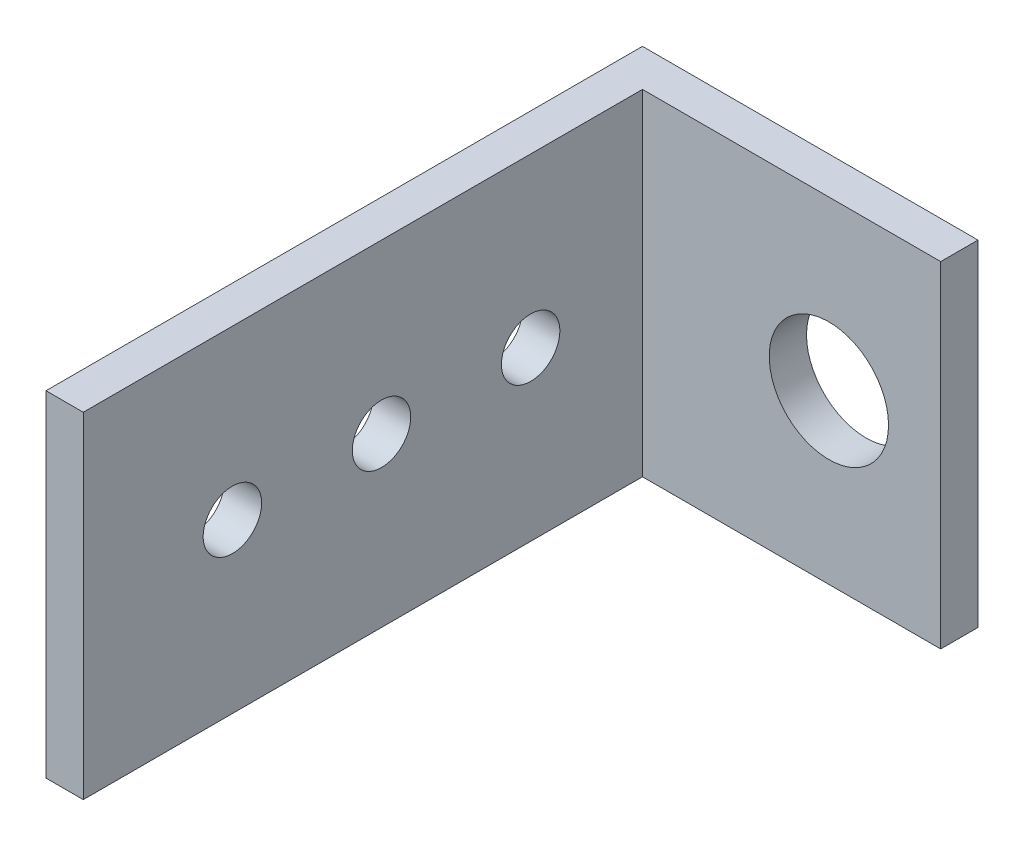
SolidWorks part; units mm, degrees
material "6061-T6 (SS)"
ref_plane "Front Plane" through (0, 0, 0) normal (0, 0, 1) x (1, 0, 0)
ref_plane "Top Plane" through (0, 0, 0) normal (0, 1, 0) x (1, 0, 0)
ref_plane "Right Plane" through (0, 0, 0) normal (1, 0, 0) x (0, 0, -1)
sketch "Sketch1" plane through (0, 0, 0) normal (0, 1, 0) x (1, 0, 0)
  line L1 (0, 0) -> (3.175, 0)
  line L2 (0, 0) -> (0, 50.8)
  line L3 (0, 50.8) -> (3.175, 50.8)
  line L4 (3.175, 0) -> (3.175, 50.8)
  line L5 (0, 50.8) -> (28.575, 50.8)
  line L6 (0, 50.8) -> (0, 47.625)
  line L7 (0, 47.625) -> (28.575, 47.625)
  line L8 (28.575, 50.8) -> (28.575, 47.625)
  dimension "D1" = 28.575
  dimension "D2" = 50.8
  dimension "D3" = 3.175
  dimension "D4" = 3.175
extrude "Boss-Extrude1" add sketch "Sketch1" along normal blind 28.575 contours L7 L2 L1 L4 | L8 L5 L4 L7 | L2 L7 L4 L3 region at (1.5875, 0, -23.8125) region at (1.5875, 0, -49.2125) region at (15.875, 0, -49.2125)
sketch "Sketch2" plane through (0, 0, -47.625) normal (0, 0, 1) x (1, 0, 0)
  line L0 (28.575, 28.575) -> (28.575, 0) construction
  circle A0 centre (19.05, 14.2875) radius 5.08
  point P4 (28.575, 14.2875)
  dimension "D1" = 10.16
  dimension "D2" = 9.525
extrude "Cut-Extrude1" cut sketch "Sketch2" against normal blind 32.766
sketch "Sketch3" plane through (3.175, 0, 0) normal (1, 0, 0) x (0, 0, -1)
  line L0 (0, 28.575) -> (0, 0) construction
  circle A0 centre (12.7, 14.2875) radius 2.4892
  circle A1 centre (25.4, 14.2875) radius 2.4892
  circle A2 centre (38.1, 14.2875) radius 2.4892
  point P5 (0, 14.2875)
  dimension "D1" = 4.9784
  dimension "D3" = 12.7
  dimension "D4" = 12.7
  dimension "D2" = 12.7
extrude "Cut-Extrude2" cut sketch "Sketch3" against normal blind 32.766
